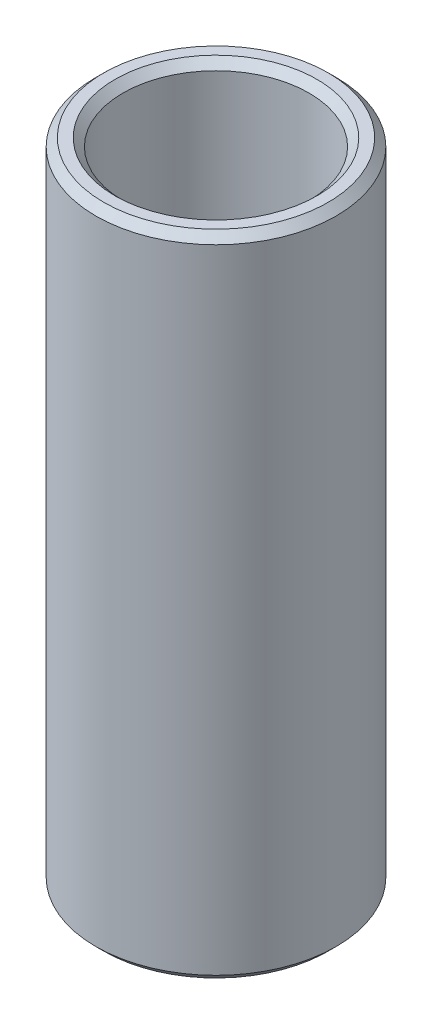
SolidWorks part; units mm, degrees
ref_plane "Front Plane" through (0, 0, 0) normal (0, 0, 1) x (1, 0, 0)
ref_plane "Top Plane" through (0, 0, 0) normal (0, 1, 0) x (1, 0, 0)
ref_plane "Right Plane" through (0, 0, 0) normal (1, 0, 0) x (0, 0, -1)
sketch "Sketch1" plane through (0, 0, 0) normal (0, 1, 0) x (1, 0, 0)
  circle A0 centre (0, 0) radius 50
  dimension "SLEEVE_OD" = 100
extrude "Boss-Extrude1" add sketch "Sketch1" along normal blind 269.9609
sketch "Sketch2" plane through (0, 0, 0) normal (0, 1, 0) x (1, 0, 0)
  circle A0 centre (0, 0) radius 38.7385
  dimension "BORE_D" = 77.4769
extrude "Cut-Extrude1" cut sketch "Sketch2" along normal through all
chamfer "Chamfer1" distance 3.2927 angle 45 4 edges at (0, 269.9609, 38.7385) (0, 0, 38.7385) (0, 0, 50) (0, 269.9609, 50)
